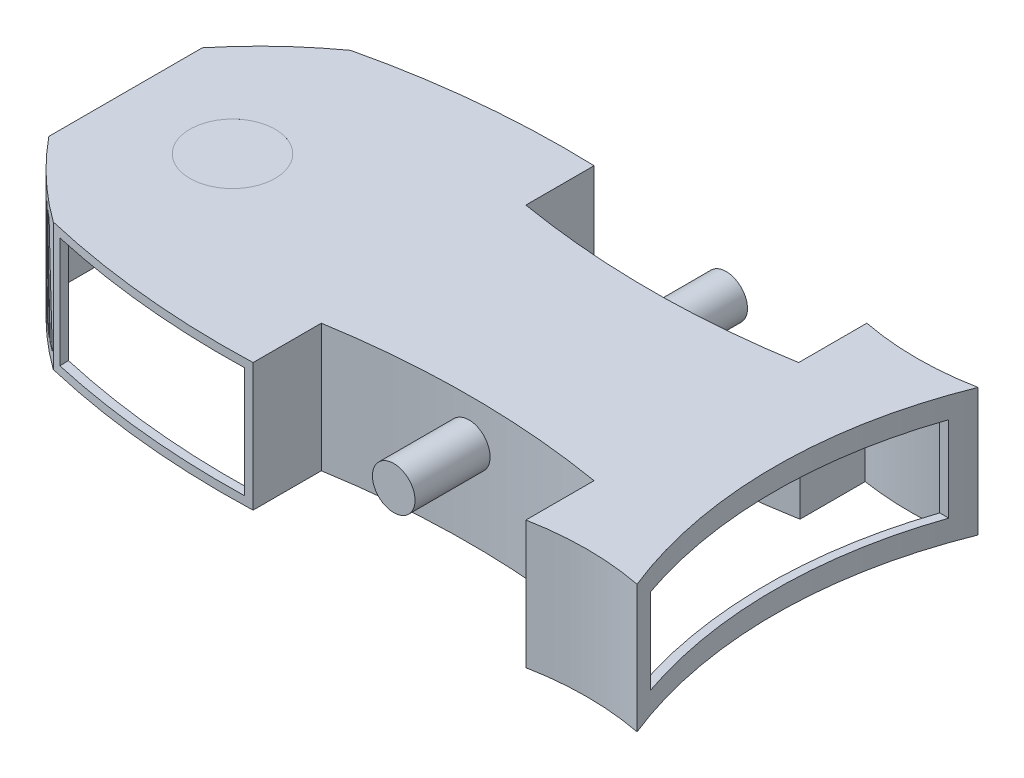
SolidWorks part; units mm, degrees
ref_plane "Front Plane" through (0, 0, 0) normal (0, 0, 1) x (1, 0, 0)
ref_plane "Top Plane" through (0, 0, 0) normal (0, 1, 0) x (1, 0, 0)
ref_plane "Right Plane" through (0, 0, 0) normal (1, 0, 0) x (0, 0, -1)
sketch "Sketch2" plane through (0, 0, 0) normal (0, 1, 0) x (1, 0, 0)
  line L0 (0, 0) -> (-110.2879, 0) construction
  line L1 (-110.2879, 0) -> (92.9121, 0) construction
  line L2 (-110.2879, -22.86) -> (-110.2879, 22.86) construction
  line L4 (-64.5922, 50.8) -> (-45.28, 50.8) construction
  line L8 (-45.28, 50.8) -> (-21.4935, 50.8) construction
  line L9 (-21.4935, 50.8) -> (-21.4935, 30.48) construction
  line L10 (-21.4935, 30.48) -> (59.7865, 30.48) construction
  line L11 (59.7865, 30.48) -> (59.7865, 50.8) construction
  line L12 (59.7865, 50.8) -> (92.9121, 50.8) construction
  line L14 (59.7865, -50.8) -> (92.9121, -50.8) construction
  line L15 (59.7865, -30.48) -> (59.7865, -50.8) construction
  line L16 (-21.4935, -30.48) -> (59.7865, -30.48) construction
  line L17 (-21.4935, -50.8) -> (-21.4935, -30.48) construction
  line L18 (-45.28, -50.8) -> (-21.4935, -50.8) construction
  line L22 (-64.5922, -50.8) -> (-45.28, -50.8) construction
  line L24 (-110.2879, 22.86) -> (-87.5445, 44.2841) construction
  line L25 (-87.5445, 44.2841) -> (-64.5922, 50.8) construction
  line L26 (-87.5445, -44.2841) -> (-64.5922, -50.8) construction
  line L27 (-110.2879, -22.86) -> (-87.5445, -44.2841) construction
  line L28 (-110.2879, 22.86) -> (-110.2879, -22.86)
  line L30 (-21.4935, 50.8) -> (-21.4935, 30.48)
  line L31 (59.7865, 50.8) -> (59.7865, 30.48)
  line L32 (-87.5445, -44.2841) -> (-64.5922, -50.8) construction
  line L33 (-110.2879, -22.86) -> (-87.5445, -44.2841) construction
  line L34 (59.7865, -50.8) -> (92.9121, -50.8) construction
  line L35 (59.7865, -30.48) -> (59.7865, -50.8) construction
  line L36 (-21.4935, -30.48) -> (59.7865, -30.48) construction
  line L37 (-21.4935, -50.8) -> (-21.4935, -30.48) construction
  line L38 (-45.28, -50.8) -> (-21.4935, -50.8) construction
  line L39 (-64.5922, -50.8) -> (-45.28, -50.8) construction
  line L40 (59.7865, -50.8) -> (59.7865, -30.48)
  line L41 (-21.4935, -50.8) -> (-21.4935, -30.48)
  arc A0 (92.9121, -50.8) -> (92.9121, 50.8) centre (219.3583, 0) cw
  arc A1 (-21.4935, 30.48) -> (59.7865, 30.48) centre (19.1465, 272.2128) ccw
  arc A2 (59.7865, 50.8) -> (92.9121, 50.8) centre (76.3493, 136.0227) ccw
  arc A3 (-21.4935, 50.8) -> (-87.5445, 44.2841) centre (-30.1985, -198.9916) ccw
  arc A4 (-87.5445, 44.2841) -> (-110.2879, 22.86) centre (-16.9499, -53.4419) ccw
  arc A5 (-87.5445, -44.2841) -> (-110.2879, -22.86) centre (-16.9499, 53.4419) cw
  arc A6 (-21.4935, -50.8) -> (-87.5445, -44.2841) centre (-30.1985, 198.9916) cw
  arc A7 (59.7865, -50.8) -> (92.9121, -50.8) centre (76.3493, -136.0227) cw
  arc A8 (-21.4935, -30.48) -> (59.7865, -30.48) centre (19.1465, -272.2128) cw
  point P31 (19.1465, 27.0876)
  point P32 (76.3493, 49.2054)
  dimension "D6" = 136.2691
  dimension "D17" = 249.9432
  dimension "D18" = 120.5569
  dimension "D1" = 203.2
  dimension "D2" = 101.6
  dimension "D3" = 20.32
  dimension "D4" = 81.28
  dimension "D5" = 50.8
  dimension "D7" = 92.9121
  dimension "D8" = 59.7865
  dimension "D9" = 64.5922
  dimension "D10" = 22.86
  dimension "D11" = 44.2841
  dimension "D12" = 87.5445
  dimension "D13" = 45.28
  dimension "D14" = 92.9121
  dimension "D15" = 27.0876
  dimension "D16" = 49.2054
extrude "Boss-Extrude2" add sketch "Sketch2" along normal blind 38.1 contours A6 A5 L28 A4 A3 L30 A1 L31 A2 A0 A7 L40 A8 L41
sketch3d "3DSketch1"
  line L0 (59.7865, 0, 30.48) -> (-21.4935, 0, 30.48) construction
  line L1 (-21.4935, 0, 30.48) -> (19.1465, 0, 30.48) construction
  line L2 (-21.4935, 38.1, 30.48) -> (59.7865, 38.1, 30.48) construction
  line L3 (59.7865, 38.1, 30.48) -> (59.7865, 0, 30.48) construction
  line L4 (59.7865, 0, 30.48) -> (-21.4935, 0, 30.48) construction
  line L5 (-21.4935, 0, 30.48) -> (-21.4935, 38.1, 30.48) construction
  line L6 (19.1465, 0, 30.48) -> (19.1465, 38.1, 30.48) construction
  line L7 (19.1465, 38.1, 30.48) -> (19.1465, 19.05, 30.48) construction
  line L8 (59.7865, 19.05, 30.48) -> (-21.4935, 19.05, 30.48) construction
  line L9 (19.1465, 19.05, 30.48) -> (19.1465, 28.575, 30.48) construction
  line L10 (19.1465, 28.575, 30.48) -> (59.7865, 28.575, 30.48) construction
  circle A2 centre (19.1465, 25.4, 30.48) radius 6.35
  point P18 (19.1465, 25.4, 36.83)
  dimension "D1" = 12.7
  dimension "D2" = 12.7
ref_plane "Plane1" through (0, 0, 50.8) normal (0, 0, -1) x (-1, 0, 0)
extrude "Boss-Extrude4" add sketch "3DSketch1" along direction (0, 0, -1) on the side of the normal mid plane 38.1 contours A2
ref_plane "Plane2" through (0, 0, 0) normal (0, 0, -1) x (-1, 0, 0)
mirror "Mirror2" about plane through (0, 0, 0) normal (0, 0, -1) of "Boss-Extrude4"
shell "Shell2" thickness 2.54 removed face at (-4.88, 0, 0)
sketch "Sketch4" plane through (0, 0, -49.53) normal (0, 0, -1) x (-1, 0, 0)
  line L0 (-19.1465, 25.4) -> (-19.1465, 38.1) construction
  line L1 (21.4935, 38.1) -> (-59.7865, 38.1) construction
  dimension "D1" = 12.7
ref_plane "Plane3" through (-87.5445, 38.1, -44.2841) normal (0, -1, 0) x (-1, 0, 0)
sketch "Sketch6" plane through (0, 38.1, 0) normal (0, 1, 0) x (1, 0, 0)
  line L0 (-110.2879, 0) -> (83.0892, 0) construction
  line L1 (-110.2879, 22.86) -> (-110.2879, -22.86) construction
  arc A0 (92.9121, 50.8) -> (92.9121, -50.8) centre (219.3583, 0) ccw construction
  circle A1 centre (-78.4248, 0) radius 12.7
  point P9 (-78.4248, 0)
  dimension "D1" = 25.4
  dimension "D2" = 31.8631
extrude "Cut-Extrude1" cut sketch "Sketch6" against normal blind 0.0025 contours A1
ref_plane "Plane4" through (-21.4935, 0, 50.8) normal (0.0348, 0, 0.9994) x (0.9994, 0, -0.0348)
sketch "Sketch7" plane through (-21.4935, 0, 50.8) normal (0.0348, 0, 0.9994) x (0.9994, 0, -0.0348)
  line L14 (-63.2439, 2.54) -> (-2.54, 2.54)
  line L15 (-2.54, 2.54) -> (-2.54, 35.56)
  line L16 (-2.54, 35.56) -> (-63.2439, 35.56)
  line L17 (-63.2439, 35.56) -> (-63.2439, 2.54)
  line L18 (-63.2439, 2.54) -> (-2.54, 2.54)
  line L19 (-2.54, 2.54) -> (-2.54, 35.56)
  line L20 (-2.54, 35.56) -> (-63.2439, 35.56)
  line L21 (-63.2439, 35.56) -> (-63.2439, 2.54)
  dimension "D1" = 2.54
extrude "Cut-Extrude2" cut sketch "Sketch7" against normal through all both and the other way through all contours L18 L19 L20 L21
ref_plane "Plane5" through (92.9121, 0, 0) normal (-1, 0, 0) x (0, 0, 1)
sketch "Sketch8" plane through (92.9121, 0, 0) normal (-1, 0, 0) x (0, 0, 1)
  line L14 (-44.45, 31.75) -> (-44.45, 6.35)
  line L15 (-44.45, 6.35) -> (44.45, 6.35)
  line L16 (44.45, 6.35) -> (44.45, 31.75)
  line L17 (44.45, 31.75) -> (-44.45, 31.75)
  line L18 (-44.45, 31.75) -> (-44.45, 6.35)
  line L19 (-44.45, 6.35) -> (44.45, 6.35)
  line L20 (44.45, 6.35) -> (44.45, 31.75)
  line L21 (44.45, 31.75) -> (-44.45, 31.75)
  dimension "D1" = 6.35
extrude "Cut-Extrude4" cut sketch "Sketch8" along normal blind 16.51 contours L18 L19 L20 L21
ref_plane "Plane6" through (-87.5445, 0, 44.2841) normal (-0.5856, 0, 0.8106) x (0.8106, 0, 0.5856)
sketch "Sketch9" plane through (-87.5445, 0, 44.2841) normal (-0.5856, 0, 0.8106) x (0.8106, 0, 0.5856)
  line L0 (-29.7116, 34.29) -> (-26.3011, 34.29)
  line L1 (-26.3011, 34.29) -> (-20.9267, 3.81)
  line L2 (-20.9267, 3.81) -> (-24.3372, 3.81)
  line L3 (-24.3372, 3.81) -> (-29.7116, 34.29)
  line L6 (0, 38.1) -> (-30.9816, 38.1) construction
  line L7 (-30.9816, 0) -> (0, 0) construction
  line L8 (-30.9816, 38.1) -> (-30.9816, 0) construction
  line L9 (-19.423, 3.81) -> (-24.7975, 34.29)
  line L10 (-24.7975, 34.29) -> (-21.387, 34.29)
  line L11 (-21.387, 34.29) -> (-16.0125, 3.81)
  line L12 (-16.0125, 3.81) -> (-19.423, 3.81)
  line L13 (-14.5088, 3.81) -> (-19.8833, 34.29)
  line L14 (-19.8833, 34.29) -> (-16.4728, 34.29)
  line L15 (-16.4728, 34.29) -> (-11.0983, 3.81)
  line L16 (-11.0983, 3.81) -> (-14.5088, 3.81)
  line L17 (-9.5947, 3.81) -> (-14.9691, 34.29)
  line L18 (-14.9691, 34.29) -> (-11.5586, 34.29)
  line L19 (-11.5586, 34.29) -> (-6.1842, 3.81)
  line L20 (-6.1842, 3.81) -> (-9.5947, 3.81)
  line L21 (-4.6805, 3.81) -> (-10.0549, 34.29)
  line L22 (-10.0549, 34.29) -> (-6.6444, 34.29)
  line L23 (-6.6444, 34.29) -> (-1.27, 3.81)
  line L24 (-1.27, 3.81) -> (-4.6805, 3.81)
  line L25 (0, 38.1) -> (0, 0) construction
  point P28 (0, 0)
  dimension "D1" = 3.4105
  dimension "D2" = 3.81
  dimension "D3" = 3.81
  dimension "D4" = 1.27
  dimension "D5" = 100
  dimension "D7" = 1.27
  dimension "D6" = 5
sketch "Sketch10" plane through (0, 35.56, 0) normal (0, -1, 0) x (1, 0, 0)
  line L0 (-107.7479, 0) -> (80.5492, 0) construction
  line L1 (-107.7479, -21.9485) -> (-107.7479, 21.9485) construction
  arc A0 (88.9506, 47.5584) -> (88.9506, -47.5584) centre (219.3583, 0) ccw construction
extrude "Cut-Extrude5" cut sketch "Sketch9" against normal mid plane 16.51
ref_plane "Plane7" through (-87.5445, 0, -44.2841) normal (0.5856, 0, 0.8106) x (0.8106, 0, -0.5856)
sketch "Sketch13" plane through (-87.5445, 0, -44.2841) normal (0.5856, 0, 0.8106) x (0.8106, 0, -0.5856)
  line L0 (-31.1145, 33.6408) -> (-27.704, 33.6408)
  line L1 (-27.704, 33.6408) -> (-22.3817, 3.4565)
  line L2 (-22.3817, 3.4565) -> (-25.7922, 3.4565)
  line L3 (-25.7922, 3.4565) -> (-31.1145, 33.6408)
  line L4 (-26.0926, 33.8437) -> (-20.7182, 3.3637)
  line L5 (-20.7182, 3.3637) -> (-17.3796, 3.3637)
  line L6 (-17.3796, 3.3637) -> (-22.7541, 33.8437)
  line L7 (-22.7541, 33.8437) -> (-26.0926, 33.8437)
  line L8 (-21.2504, 33.8437) -> (-15.876, 3.3637)
  line L9 (-15.876, 3.3637) -> (-12.4655, 3.3637)
  line L10 (-12.4655, 3.3637) -> (-17.8399, 33.8437)
  line L11 (-17.8399, 33.8437) -> (-21.2504, 33.8437)
  line L12 (-16.3362, 33.8437) -> (-10.9618, 3.3637)
  line L13 (-10.9618, 3.3637) -> (-7.5513, 3.3637)
  line L14 (-7.5513, 3.3637) -> (-12.9257, 33.8437)
  line L15 (-12.9257, 33.8437) -> (-16.3362, 33.8437)
  line L16 (-11.4221, 33.8437) -> (-6.0476, 3.3637)
  line L17 (-6.0476, 3.3637) -> (-2.6371, 3.3637)
  line L18 (-2.6371, 3.3637) -> (-8.0116, 33.8437)
  line L19 (-8.0116, 33.8437) -> (-11.4221, 33.8437)
  point P20 (0, 0)
  point P21 (0, 0)
  dimension "D1" = 3.4105
  dimension "D2" = 100
  dimension "D3" = 47.6711
  dimension "D4" = 52.5853
  dimension "D5" = 53.0455
  dimension "D6" = 57.4994
  dimension "D7" = 62.4136
  dimension "D8" = 65.7521
  dimension "D9" = 67.4157
  dimension "D10" = 72.738
  dimension "D11" = 3.3637
  dimension "D12" = 3.4565
extrude "Cut-Extrude6" cut sketch "Sketch13" against normal mid plane 16.51
